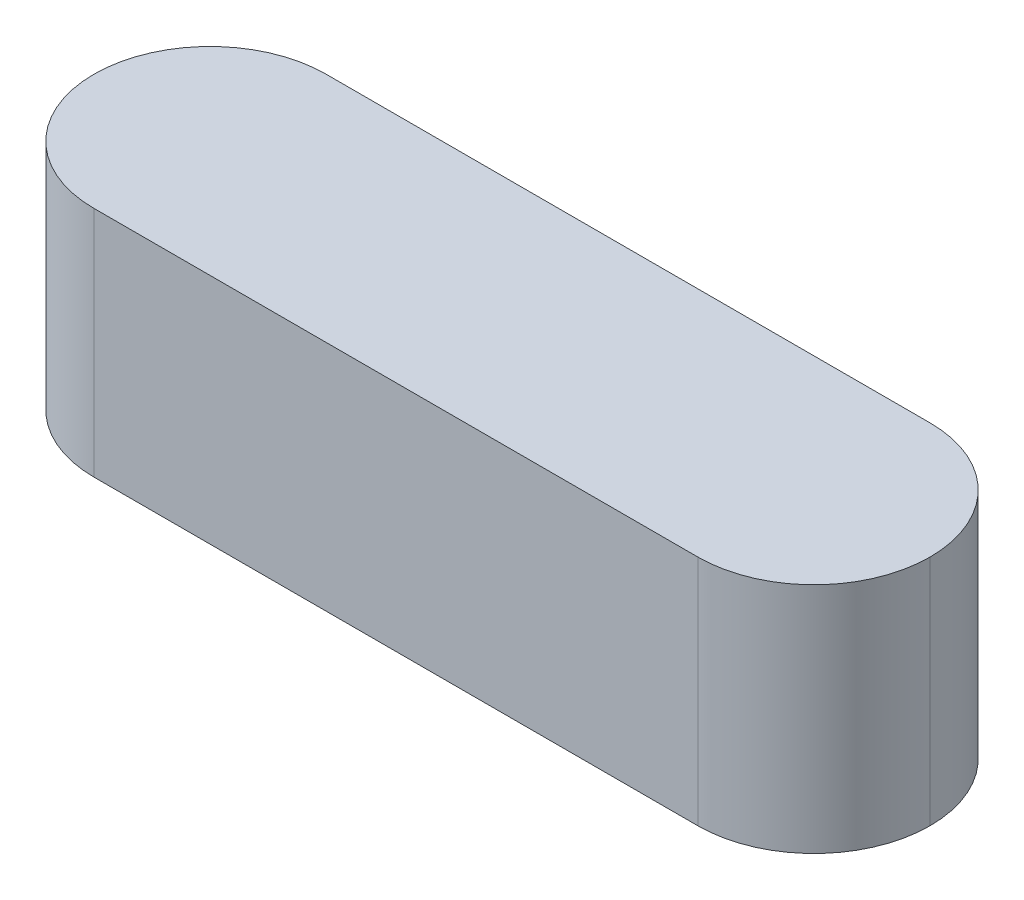
SolidWorks part; units mm, degrees
ref_plane "Front Plane" through (0, 0, 0) normal (0, 0, 1) x (1, 0, 0)
ref_plane "Top Plane" through (0, 0, 0) normal (0, 1, 0) x (1, 0, 0)
ref_plane "Right Plane" through (0, 0, 0) normal (1, 0, 0) x (0, 0, -1)
sketch "Sketch1" plane through (0, 0, 0) normal (0, 1, 0) x (1, 0, 0)
  line L1 (0, 0) -> (90, 0)
  line L2 (0, 0) -> (0, 25)
  line L3 (0, 25) -> (90, 25)
  line L4 (90, 0) -> (90, 25)
  dimension "D1" = 90
  dimension "D2" = 25
extrude "Boss-Extrude1" add sketch "Sketch1" along normal blind 25.05 contours L3 L4 L1 L2
fillet "Fillet1" radius 12.5 4 edges at (90, 12.525, 0) (90, 12.525, -25) (0, 12.525, 0) (0, 12.525, -25)
sketch "Sketch2" plane through (0, 0, 0) normal (0, -1, 0) x (1, 0, 0)
  line L0 (22.5, -12.5) -> (67.5, -12.5) construction
  line L1 (45, -12.5) -> (45, 0) construction
  line L2 (12.5, 0) -> (77.5, 0) construction
  line L3 (45, -12.5) -> (45, -25) construction
  line L4 (12.5, -25) -> (77.5, -25) construction
  circle A0 centre (22.5, -12.5) radius 1.5
  circle A1 centre (67.5, -12.5) radius 1.5
  dimension "D2" = 3
  dimension "D3" = 3
  dimension "D1" = 45
extrude "Cut-Extrude1" cut sketch "Sketch2" against normal blind 5
